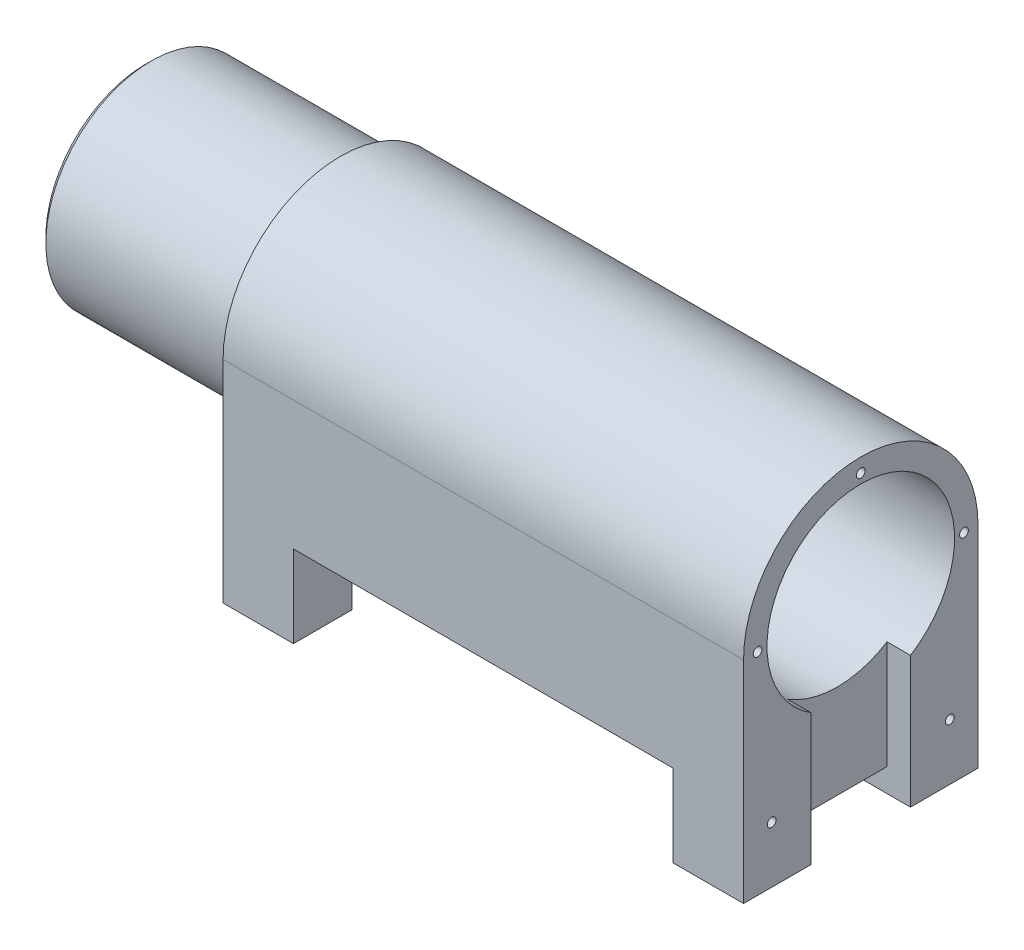
SolidWorks part; units mm, degrees
material "6061-T6 (SS)"
ref_plane "Front Plane" through (0, 0, 0) normal (0, 0, 1) x (1, 0, 0)
ref_plane "Top Plane" through (0, 0, 0) normal (0, 1, 0) x (1, 0, 0)
ref_plane "Right Plane" through (0, 0, 0) normal (1, 0, 0) x (0, 0, -1)
sketch "Sketch1" plane through (0, 0, 0) normal (1, 0, 0) x (0, 0, -1)
  line L1 (-15.875, -22.225) -> (15.875, -22.225)
  line L2 (-15.875, -22.225) -> (-15.875, 22.225)
  line L3 (-15.875, 22.225) -> (15.875, 22.225)
  line L4 (15.875, -22.225) -> (15.875, 22.225)
  line L5 (-15.875, -22.225) -> (15.875, 22.225) construction
  line L6 (-15.875, 22.225) -> (15.875, -22.225) construction
  point P0 (0, 0)
  dimension "D1" = 44.45
  dimension "D2" = 31.75
extrude "Boss-Extrude1" add sketch "Sketch1" along normal mid plane 96.8375
sketch "Sketch2" plane through (48.4187, 0, 0) normal (1, 0, 0) x (0, 0, -1)
  line L0 (15.875, 22.225) -> (-15.875, 22.225) construction
  line L1 (-15.875, 22.225) -> (-15.875, -22.225) construction
  line L2 (15.875, -22.225) -> (15.875, 22.225) construction
  line L3 (-15.875, 6.35) -> (-15.875, 22.225)
  line L4 (-15.875, 22.225) -> (0, 22.225)
  line L5 (0, 22.225) -> (15.875, 22.225)
  line L6 (15.875, 22.225) -> (15.875, 6.35)
  arc A0 (15.875, 6.35) -> (-15.875, 6.35) centre (0, 6.35) ccw
  line M1 (15.875, -22.225) -> (15.875, 22.225)
  line M2 (15.875, 22.225) -> (-15.875, 22.225)
  line M3 (-15.875, 22.225) -> (-15.875, -22.225)
extrude "Cut-Extrude1" cut sketch "Sketch2" against normal up to next contours A0 M2 M3 | A0 M1 M2 region at (48.4187, 18.679, -12.329) region at (48.4187, 18.679, 12.329)
sketch "Sketch3" plane through (0, -22.225, 0) normal (0, -1, 0) x (1, 0, 0)
  line L0 (48.4187, 15.875) -> (-48.4187, 15.875) construction
  line L1 (38.8937, 15.875) -> (-12.5412, 15.875)
  line L2 (38.8937, 15.875) -> (38.8938, -19.05)
  line L3 (38.8938, -19.05) -> (-12.5412, -19.05)
  line L4 (-12.5412, 15.875) -> (-12.5412, -19.05)
  line L6 (48.4187, 15.875) -> (48.4187, -15.875) construction
  dimension "D1" = 9.525
  dimension "D2" = 51.435
extrude "Cut-Extrude2" cut sketch "Sketch3" against normal blind 11.1125
sketch "Sketch4" plane through (0, -22.225, 0) normal (0, -1, 0) x (1, 0, 0)
  line L0 (-12.5412, 15.875) -> (-48.4187, 15.875) construction
  line L1 (-22.0662, 15.875) -> (-48.4187, 15.875)
  line L2 (-22.0662, 15.875) -> (-22.0662, -15.875)
  line L3 (-22.0662, -15.875) -> (-48.4187, -15.875)
  line L4 (-48.4187, 15.875) -> (-48.4187, -15.875)
  line L5 (-12.5412, 15.875) -> (-12.5412, -15.875) construction
  dimension "D1" = 9.525
extrude "Cut-Extrude3" cut sketch "Sketch4" against normal up to surface (11.1125 mm away) up to face at (13.1763, -11.1125, 0)
sketch "Sketch5" plane through (-48.4187, 0, 0) normal (-1, 0, 0) x (0, 0, 1)
  line L1 (-15.875, -22.225) -> (15.875, -22.225) construction
  line L5 (-15.875, -11.1125) -> (15.875, -11.1125)
  line L6 (15.875, -11.1125) -> (15.875, 6.35)
  line L7 (-15.875, 6.35) -> (-15.875, -11.1125)
  line L8 (-15.875, -22.225) -> (15.875, -22.225)
  line L9 (15.875, -22.225) -> (15.875, 6.35)
  line L10 (-15.875, 6.35) -> (-15.875, -22.225)
  circle A0 centre (0, 6.35) radius 14.2875
  arc A2 (15.875, 6.35) -> (-15.875, 6.35) centre (0, 6.35) ccw
  arc A3 (15.875, 6.35) -> (-15.875, 6.35) centre (0, 6.35) ccw
  dimension "D1" = 28.575
  dimension "D3" = 0
extrude "Cut-Extrude6" cut sketch "Sketch5" against normal up to surface (26.3525 mm away) up to face at (-22.0662, -16.6687, 0)
sketch "Sketch6" plane through (48.4187, 0, 0) normal (1, 0, 0) x (0, 0, -1)
  circle A0 centre (0, 6.35) radius 12.7
  arc A1 (15.875, 6.35) -> (-15.875, 6.35) centre (0, 6.35) ccw construction
  dimension "D1" = 25.4
extrude "Cut-Extrude7" cut sketch "Sketch6" against normal offset from surface (93.0275 mm away) 3.81 up to face at (-48.4187, 6.35, 14.2875)
chamfer "Chamfer1" distance 0.762 angle 45 1 edges at (-48.4187, 6.35, 14.2875)
sketch "Sketch7" plane through (48.4187, 0, 0) normal (1, 0, 0) x (0, 0, -1)
  line L0 (-15.875, -22.225) -> (15.875, -22.225) construction
  line L1 (-6.731, -22.225) -> (6.731, -22.225)
  line L2 (-6.731, -22.225) -> (-6.731, -4.4196)
  line L3 (-6.731, -4.4196) -> (6.731, -4.4196)
  line L4 (6.731, -22.225) -> (6.731, -4.4196)
  line L5 (-6.731, -22.225) -> (6.731, -4.4196) construction
  line L6 (-6.731, -4.4196) -> (6.731, -22.225) construction
  circle A0 centre (0, 6.35) radius 12.7 construction
  point P0 (0, -13.3223)
  dimension "D1" = 13.462
extrude "Cut-Extrude8" cut sketch "Sketch7" against normal blind 3.175
sketch "Sketch8" plane through (0, -22.225, 0) normal (0, -1, 0) x (1, 0, 0)
  line L0 (38.8938, -15.875) -> (38.8937, 15.875) construction
  line L1 (38.8938, 6.731) -> (45.2438, 6.731)
  line L2 (38.8938, 6.731) -> (38.8937, -6.731)
  line L3 (38.8937, -6.731) -> (45.2437, -6.731)
  line L4 (45.2438, 6.731) -> (45.2437, -6.731)
  line L5 (45.2437, 6.731) -> (45.2437, -6.731) construction
  line L6 (45.2438, -6.731) -> (45.2437, 6.731) construction
  line L7 (45.2437, 6.731) -> (48.4187, 6.731) construction
  line L8 (45.2437, -6.731) -> (48.4187, -6.731) construction
extrude "Cut-Extrude9" cut sketch "Sketch8" against normal blind 3.175
sketch "Sketch9" plane through (-22.0662, 0, 0) normal (-1, 0, 0) x (0, 0, 1)
  line L0 (-15.875, -22.225) -> (15.875, -22.225) construction
  line L1 (-7.9375, -12.7) -> (7.9375, -12.7)
  line L2 (-7.9375, -12.7) -> (-7.9375, -22.225)
  line L3 (-7.9375, -22.225) -> (7.9375, -22.225)
  line L4 (7.9375, -12.7) -> (7.9375, -22.225)
  line L5 (-7.9375, -12.7) -> (7.9375, -22.225) construction
  line L6 (-7.9375, -22.225) -> (7.9375, -12.7) construction
  point P0 (0, -17.4625)
  dimension "D1" = 15.875
  dimension "D2" = 9.525
extrude "Cut-Extrude10" cut sketch "Sketch9" against normal up to next
fillet "Fillet1" radius 3.175 2 edges at (-17.3037, -12.7, 7.9375) (-17.3037, -12.7, -7.9375)
sketch "Sketch10" plane through (-48.4187, 0, 0) normal (-1, 0, 0) x (0, 0, 1)
  circle A0 centre (0, 6.35) radius 5.0038
  dimension "D1" = 10.0076
extrude "Cut-Extrude11" cut sketch "Sketch10" against normal through all
hole_wizard "CSK for M2.5 Flat Head Machine Screw1" positions "Sketch13" profile "Sketch12" countersink size "M2.5" standard "Ansi Metric" end condition through all
sketch "Sketch13" plane through (-48.4187, 0, 0) normal (-1, 0, 0) x (0, 0, 1)
  line L0 (0, -7.9375) -> (0, 20.6375) construction
  line L1 (0, 6.35) -> (-4.8866, -7.0759) construction
  circle A0 centre (0, 6.35) radius 14.2875 construction
  circle A3 centre (0, 6.35) radius 14.2875 construction
  point P0 (-2.3941, -0.2278)
  dimension "D1" = 7
  dimension "D2" = 20
sketch "Sketch12" plane through (-48.4187, -0.2278, -2.3941) normal (0, 1, 0) x (0, 0, 1)
  line L0 (0, 0) -> (0, 96.8375)
  line L1 (0, 96.8375) -> (1.45, 96.8375)
  line L2 (1.45, 96.8375) -> (1.45, 1.3)
  line L3 (1.45, 1.3) -> (2.75, 0)
  line L5 (2.75, 0) -> (0, 0)
  line L6 (-1.45, 1.3) -> (-2.75, 0) construction
  line L11 (0, -6.35) -> (0, 107.95) construction
  dimension "Thru Hole Dia." = 2.9
  dimension "Thru Hole Depth" = 96.8375
  dimension "Near C'Sink Dia." = 5.5
  dimension "Near C'Sink Angle" = 90
pattern_circular "CirPattern1" count 3 over 360 about axis through (-48.4187, 6.35, 0) along (-1, 0, 0) of "CSK for M2.5 Flat Head Machine Screw1"
hole_wizard "#4-40 Tapped Hole1" positions "Sketch15" profile "Sketch14" tap size "#4-40" standard "Ansi Inch"
sketch "Sketch15" plane through (-22.0662, 0, 0) normal (-1, 0, 0) x (0, 0, 1)
  line L0 (-15.875, -22.225) -> (-7.9375, -22.225) construction
  line L1 (-15.875, 6.35) -> (-15.875, -22.225) construction
  line L2 (15.875, 6.35) -> (15.875, -22.225) construction
  point P0 (-13.335, -12.065)
  point P1 (13.335, -12.065)
  dimension "D1" = 10.16
  dimension "D2" = 2.54
  dimension "D3" = 2.54
sketch "Sketch14" plane through (-22.0662, -12.065, -13.335) normal (0, 1, 0) x (0, 0, 1)
  line L0 (0, 0) -> (0, 8.2992)
  line L1 (0, 8.2992) -> (1.1303, 7.62)
  line L2 (1.1303, 7.62) -> (1.1303, 0)
  line L5 (1.1303, 0) -> (0, 0)
  line L10 (0, 8.2992) -> (-1.1303, 7.62) construction
  line L11 (0, -6.35) -> (0, 107.95) construction
  dimension "Tap Drill Dia." = 2.2606
  dimension "Tap Drill Depth" = 7.62
  dimension "Drill Angle" = 118
cosmetic thread "Hole Thread1" parameters "D1"=5.588, "D2"=2.8448
cosmetic thread "Hole Thread2" parameters "D1"=5.588, "D2"=2.8448
hole_wizard "#0-80 Tapped Hole1" positions "Sketch18" profile "Sketch17" tap size "#0-80" standard "Ansi Inch"
sketch "Sketch18" plane through (48.4187, 0, 0) normal (1, 0, 0) x (0, 0, -1)
  line L0 (-15.875, -22.225) -> (-6.731, -22.225) construction
  line L2 (-15.875, 6.35) -> (-15.875, -22.225) construction
  line L3 (15.875, -22.225) -> (15.875, 6.35) construction
  circle A0 centre (0, 6.35) radius 13.97 construction
  point P0 (-12.065, -14.605)
  point P1 (12.065, -14.605)
  point P8 (0, 20.32)
  point P10 (-13.97, 6.35)
  point P12 (13.97, 6.35)
  dimension "D1" = 27.94
  dimension "D2" = 7.62
  dimension "D3" = 3.81
  dimension "D4" = 3.81
sketch "Sketch17" plane through (48.4187, -14.605, 12.065) normal (0, 1, 0) x (0, 0, -1)
  line L0 (0, 0) -> (0, 6.4539)
  line L1 (0, 6.4539) -> (0.5956, 6.096)
  line L2 (0.5956, 6.096) -> (0.5956, 0)
  line L5 (0.5956, 0) -> (0, 0)
  line L10 (0, 6.4539) -> (-0.5956, 6.096) construction
  line L11 (0, -6.35) -> (0, 107.95) construction
  dimension "Tap Drill Dia." = 1.1913
  dimension "Tap Drill Depth" = 6.096
  dimension "Drill Angle" = 118
cosmetic thread "Hole Thread3" parameters "D1"=5.08, "D2"=1.524
cosmetic thread "Hole Thread4" parameters "D1"=5.08, "D2"=1.524
cosmetic thread "Hole Thread5" parameters "D1"=5.08, "D2"=1.524
cosmetic thread "Hole Thread6" parameters "D1"=5.08, "D2"=1.524
cosmetic thread "Hole Thread7" parameters "D1"=5.08, "D2"=1.524
hole_wizard "#8-32 Tapped Hole1" positions "Sketch20" profile "Sketch19" tap size "#8-32" standard "Ansi Inch"
sketch "Sketch20" plane through (0, -22.225, 0) normal (0, -1, 0) x (1, 0, 0)
  line L0 (-12.5412, 15.875) -> (-22.0662, 15.875) construction
  line L1 (-22.0662, 11.9063) -> (-12.5412, 11.9063) construction
  line L2 (-22.0662, 7.9375) -> (-22.0662, 15.875) construction
  line L3 (-12.5412, 15.875) -> (-12.5412, 7.9375) construction
  line L4 (-22.0662, -11.9062) -> (-12.5412, -11.9062) construction
  line L5 (-22.0662, -15.875) -> (-22.0662, -7.9375) construction
  line L6 (-12.5412, -7.9375) -> (-12.5412, -15.875) construction
  line L8 (43.6562, 15.875) -> (43.6562, -15.875) construction
  line L9 (48.4187, 15.875) -> (38.8937, 15.875) construction
  line L10 (48.4187, -15.875) -> (38.8938, -15.875) construction
  point P0 (-17.3037, 11.9063)
  point P4 (-17.3037, 15.875)
  point P28 (43.6562, 11.9063)
  point P30 (-17.3037, -11.9062)
  point P32 (43.6562, -11.9062)
sketch "Sketch19" plane through (-17.3037, -22.225, 11.9063) normal (1, 0, 0) x (0, 0, -1)
  line L0 (0, 0) -> (0, 8.1498)
  line L1 (0, 8.1498) -> (1.7272, 7.112)
  line L2 (1.7272, 7.112) -> (1.7272, 0)
  line L5 (1.7272, 0) -> (0, 0)
  line L10 (0, 8.1498) -> (-1.7272, 7.112) construction
  line L11 (0, -6.35) -> (0, 107.95) construction
  dimension "Tap Drill Dia." = 3.4544
  dimension "Tap Drill Depth" = 7.112
  dimension "Drill Angle" = 118
cosmetic thread "Hole Thread8" parameters "D1"=4.826, "D2"=4.1656
cosmetic thread "Hole Thread9" parameters "D1"=4.826, "D2"=4.1656
cosmetic thread "Hole Thread10" parameters "D1"=4.826, "D2"=4.1656
cosmetic thread "Hole Thread11" parameters "D1"=4.826, "D2"=4.1656
